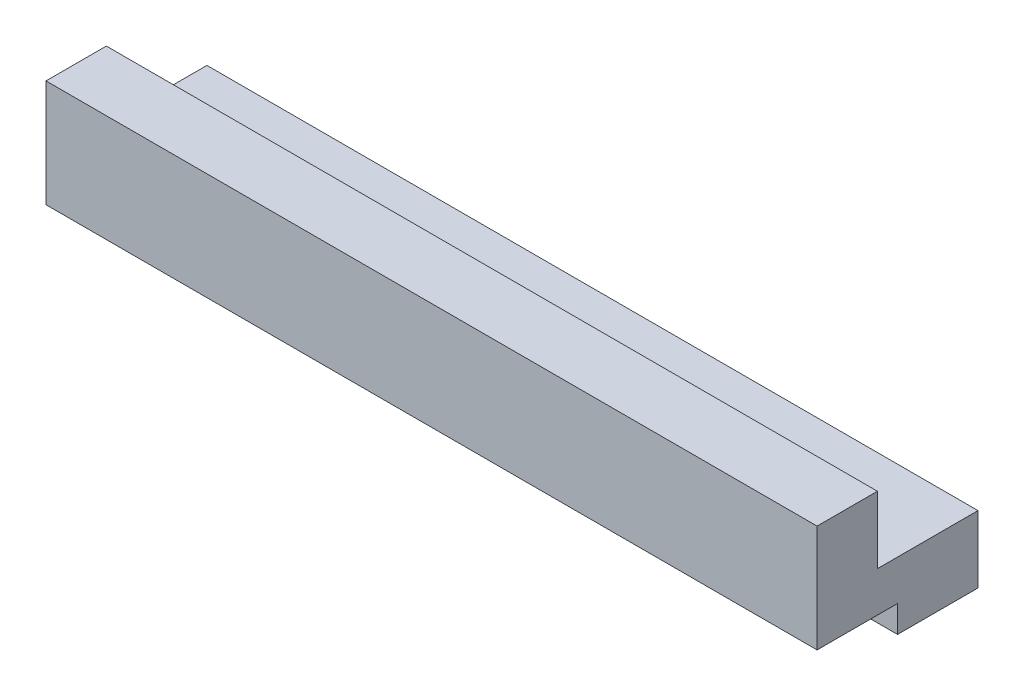
SolidWorks part; units mm, degrees
ref_plane "Front Plane" through (0, 0, 0) normal (0, 0, 1) x (1, 0, 0)
ref_plane "Top Plane" through (0, 0, 0) normal (0, 1, 0) x (1, 0, 0)
ref_plane "Right Plane" through (0, 0, 0) normal (1, 0, 0) x (0, 0, -1)
sketch "Sketch1" plane through (0, 0, 0) normal (0, 1, 0) x (1, 0, 0)
  line L1 (-18.8961, 0.4079) -> (10.3139, 0.4079)
  line L2 (-18.8961, 0.4079) -> (-18.8961, 2.6939)
  line L3 (-18.8961, 2.6939) -> (10.3139, 2.6939)
  line L4 (10.3139, 0.4079) -> (10.3139, 2.6939)
  dimension "D1" = 2.286
  dimension "D2" = 29.21
extrude "Boss-Extrude1" add sketch "Sketch1" along normal blind 4.064
sketch "Sketch2" plane through (0, 4.064, 0) normal (0, 1, 0) x (1, 0, 0)
  line L0 (-18.8961, 2.6939) -> (-18.8961, 0.4079) construction
  line L1 (10.3139, 0.4079) -> (-18.8961, 0.4079)
  line L2 (10.3139, 0.4079) -> (10.3139, 2.6939)
  line L3 (10.3139, 2.6939) -> (-18.8961, 2.6939)
  line L4 (-18.8961, 0.4079) -> (-18.8961, 2.6939)
  point P8 (-18.8961, 1.5509)
sketch "Sketch3" plane through (0, 0, -2.6939) normal (0, 0, -1) x (-1, 0, 0)
  line L0 (-10.3139, 4.064) -> (-10.3139, 0) construction
  line L1 (18.8961, 1.524) -> (-10.3139, 1.524)
  line L2 (18.8961, 1.524) -> (18.8961, -1.016)
  line L3 (18.8961, -1.016) -> (-10.3139, -1.016)
  line L4 (-10.3139, 1.524) -> (-10.3139, -1.016)
  line L5 (18.8961, 4.064) -> (18.8961, 0) construction
  line L6 (-10.3139, 0) -> (18.8961, 0) construction
  point P9 (18.8961, 2.032)
  dimension "D1" = 2.54
  dimension "D2" = 1.524
extrude "Boss-Extrude3" add sketch "Sketch3" along normal blind 3.81
sketch "Sketch4" plane through (-18.8961, 0, 0) normal (-1, 0, 0) x (0, 0, 1)
  line L1 (-2.6939, -1.016) -> (-3.4559, -1.016)
  line L2 (-2.6939, -1.016) -> (-2.6939, 0)
  line L3 (-2.6939, 0) -> (-3.4559, 0)
  line L4 (-3.4559, -1.016) -> (-3.4559, 0)
  dimension "D1" = 0.762
extrude "Cut-Extrude1" cut sketch "Sketch4" against normal blind 30.734
